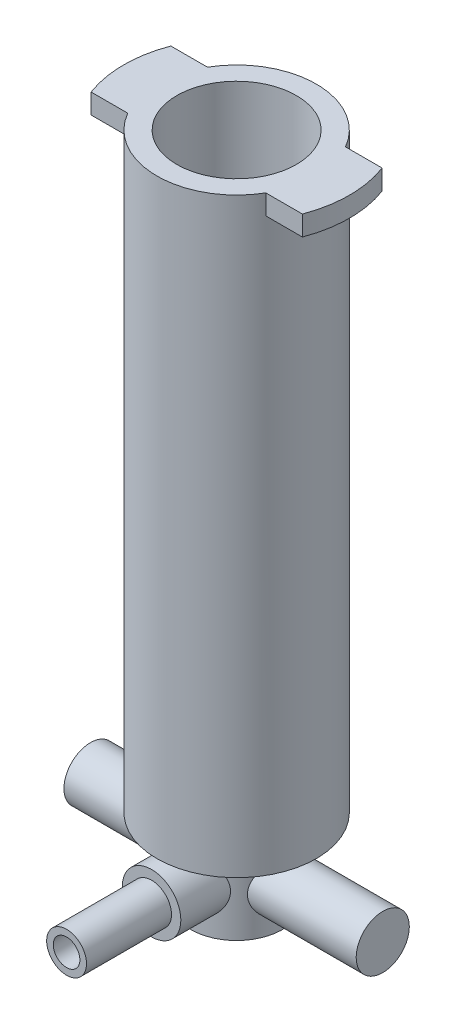
SolidWorks part; units mm, degrees
ref_plane "Front Plane" through (0, 0, 0) normal (0, 0, 1) x (1, 0, 0)
ref_plane "Top Plane" through (0, 0, 0) normal (0, 1, 0) x (1, 0, 0)
ref_plane "Right Plane" through (0, 0, 0) normal (1, 0, 0) x (0, 0, -1)
sketch "Sketch1" plane through (0, 0, 0) normal (0, 1, 0) x (1, 0, 0)
  circle A0 centre (0, 0) radius 6
extrude "Boss-Extrude1" add sketch "Sketch1" along normal blind 44.5
shell "Shell1" thickness 1.5 removed face at (0, 44.5, 6)
sketch "Sketch3" plane through (0, 0, 0) normal (0, -1, 0) x (1, 0, 0)
  circle A0 centre (0, 0) radius 3.45
extrude "Boss-Extrude3" add sketch "Sketch3" along normal blind 5.9
shell "Shell2" thickness 1.5 removed face at (0, 1.5, 4.5)
sketch "Sketch5" plane through (0, 0, 0) normal (0, 0, 1) x (1, 0, 0)
  line L0 (0, -5.9) -> (0, 0) construction
  circle A0 centre (0, -2.7032) radius 2.2
  point P4 (0, -2.3428)
  point P5 (0, 0)
  point P6 (0, -3.1468)
  point P7 (0, 0)
  point P8 (0, -2.7032)
extrude "Boss-Extrude4" add sketch "Sketch5" along normal blind 6.4
sketch "Sketch6" plane through (0, 0, 6.4) normal (0, 0, 1) x (1, 0, 0)
  circle A0 centre (0, -2.7032) radius 1.5
extrude "Boss-Extrude5" add sketch "Sketch6" along normal blind 6.4
sketch "Sketch7" plane through (0, 0, 12.8) normal (0, 0, 1) x (1, 0, 0)
  circle A0 centre (0, -2.7032) radius 1
extrude "Cut-Extrude1" cut sketch "Sketch7" against normal blind 12.4
sketch "Sketch8" plane through (0, -4.4, 0) normal (0, 1, 0) x (1, 0, 0)
  circle A0 centre (0, 0) radius 1.95
extrude "Cut-Extrude2" cut sketch "Sketch8" along normal through all
sketch "Sketch9" plane through (0, 0, 0) normal (1, 0, 0) x (0, 0, -1)
  line L0 (0, 0) -> (0, -5.869) construction
  circle A0 centre (0, -2.9345) radius 2
extrude "Boss-Extrude6" add sketch "Sketch9" along normal blind 11
sketch "Sketch10" plane through (0, -4.4, 0) normal (0, 1, 0) x (1, 0, 0)
  line L0 (0, 1.95) -> (0, -2) construction
  circle A0 centre (0, -0.025) radius 1.975
extrude "Cut-Extrude3" cut sketch "Sketch10" along normal through all contours A0
sketch "Sketch11" plane through (0, 0, 12.8) normal (0, 0, 1) x (1, 0, 0)
  circle A0 centre (0, -2.7032) radius 1
extrude "Cut-Extrude4" cut sketch "Sketch11" against normal blind 12
mirror "Mirror5" about plane through (0, 0, 0) normal (1, 0, 0) of bodies 111
sketch "Sketch13" plane through (0, 44.5, 0) normal (0, 1, 0) x (1, 0, 0)
  line L0 (-5.1962, -3) -> (-7.953, -3)
  line L1 (-5.1962, 3) -> (-7.953, 3)
  line L3 (0, 1.1598) -> (0, 0.6036) construction
  line L4 (5.1962, -3) -> (7.953, -3)
  line L5 (5.1962, 3) -> (7.953, 3)
  arc A0 (-7.953, 3) -> (-7.953, -3) centre (0, 0) ccw
  arc A1 (-5.1962, -3) -> (-5.1962, 3) centre (0, 0) cw
  arc A3 (7.953, 3) -> (7.953, -3) centre (0, 0) cw
  arc A4 (5.1962, -3) -> (5.1962, 3) centre (0, 0) ccw
extrude "Boss-Extrude8" add sketch "Sketch13" against normal blind 1.5
